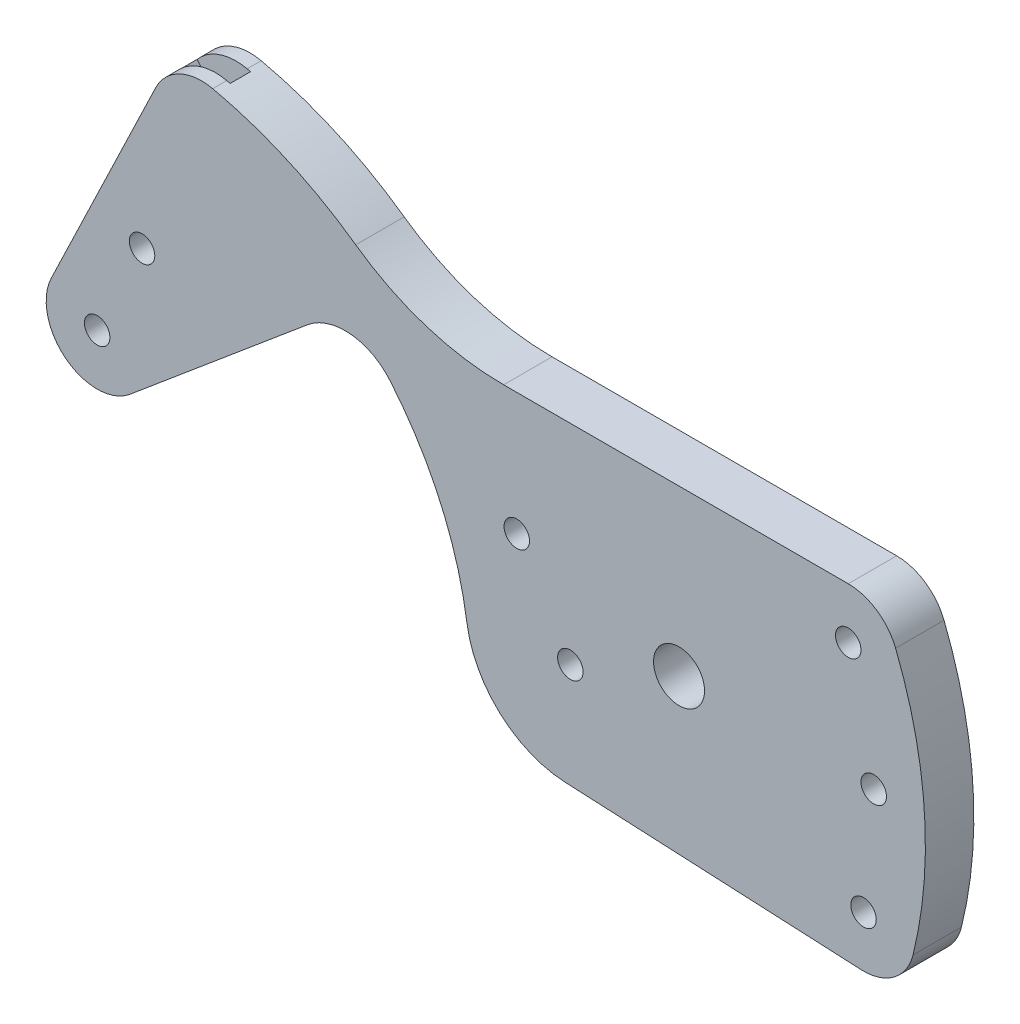
SolidWorks part; units mm, degrees
ref_plane "Front Plane" through (0, 0, 0) normal (0, 0, 1) x (1, 0, 0)
ref_plane "Top Plane" through (0, 0, 0) normal (0, 1, 0) x (1, 0, 0)
ref_plane "Right Plane" through (0, 0, 0) normal (1, 0, 0) x (0, 0, -1)
sketch "Sketch1" plane through (0, 0, 0) normal (0, 0, 1) x (1, 0, 0)
  line L1 (-5, -5) -> (5, -5) construction
  line L2 (-5, -5) -> (-5, 5) construction
  line L3 (-5, 5) -> (5, 5) construction
  line L4 (5, -5) -> (5, 5) construction
  line L5 (-5, -5) -> (5, 5) construction
  line L6 (-5, 5) -> (5, -5) construction
  line L7 (35.6989, -31.9883) -> (-22.3088, -29.1817)
  line L9 (-114.3299, 24.3337) -> (-123.1299, 6.0337)
  line L10 (-107.6899, -5.9604) -> (-72.8648, 23.2613)
  line L11 (-114.3299, 24.3337) -> (-102.6393, 48.6449)
  line L16 (-65.4725, 14.4515) -> (-108.3178, -21.5) construction
  line L17 (50.9822, -33.5) -> (-177.2181, -33.5) construction
  line L20 (-34.3975, 32.3) -> (33.1822, 32.3)
  circle A0 centre (0, 0) radius 5
  circle A1 centre (-31.8178, 8.3) radius 2.5
  circle A2 centre (-21.3178, -8.7) radius 2.5
  circle A3 centre (33.1822, 22.3) radius 2.5
  circle A4 centre (38.1822, -0.1) radius 2.5
  circle A5 centre (36.1822, -22) radius 2.5
  circle A6 centre (36.1822, -22) radius 2.5 construction
  circle A7 centre (38.1822, -0.1) radius 2.5 construction
  circle A8 centre (33.1822, 22.3) radius 2.5 construction
  circle A9 centre (-31.8178, 8.3) radius 2.5 construction
  circle A10 centre (-21.3178, -8.7) radius 2.5 construction
  arc A12 (-41.605, -11.6848) -> (-22.3088, -29.1817) centre (-21.3178, -8.7) ccw
  arc A13 (32.976, -31.8566) -> (28.2895, 32.3) centre (-34.3029, -4.5217) ccw construction
  arc A14 (45.8883, -24.4068) -> (42.4751, 25.9934) centre (-34.3029, -4.5217) ccw
  arc A15 (35.6989, -31.9883) -> (45.8883, -24.4068) centre (36.1822, -22) ccw
  arc A16 (42.4751, 25.9934) -> (33.1822, 32.3) centre (33.1822, 22.3) ccw
  circle A17 centre (-105.3178, 20) radius 2.5
  circle A18 centre (-34.3029, -4.5217) radius 82.6199 construction
  circle A19 centre (-114.1178, 1.7) radius 2.5
  circle A21 centre (-105.3178, 20) radius 2.5 construction
  circle A22 centre (-114.1178, 1.7) radius 2.5 construction
  circle A23 centre (-105.3178, 20) radius 10 construction
  arc A24 (-123.1299, 6.0337) -> (-107.6899, -5.9604) centre (-114.1178, 1.7) ccw
  arc A27 (-91.4485, 54.071) -> (-102.6393, 48.6449) centre (-93.6271, 44.3112) ccw
  circle A31 centre (-34.3029, -4.5217) radius 72.6199 construction
  arc A32 (-41.605, -11.6848) -> (-56.6627, 21.8438) centre (-108.3178, -21.5) ccw
  arc A33 (-31.0644, -26.7412) -> (-91.4485, 54.071) centre (-108.3178, -21.5) ccw
  arc A34 (-63.4016, 41.5721) -> (-34.3975, 32.3) centre (-34.3975, 82.3) ccw
  arc A35 (-56.6627, 21.8438) -> (-72.8648, 23.2613) centre (-65.4725, 14.4515) ccw
  circle A36 centre (-65.4725, 14.4515) radius 10.5004 construction
  circle A37 centre (-108.3178, -21.5) radius 67.4309 construction
  circle A38 centre (-108.3178, -21.5) radius 77.4309 construction
  circle A39 centre (-108.3178, -21.5) radius 10.5004 construction
  circle A40 centre (-108.3178, -21.5) radius 11.5004 construction
  circle A41 centre (0, 0) radius 33 construction
  point P35 (50.3427, -4.5217)
  point P37 (37.1696, 16.7103)
  point P53 (0, 0)
  point P54 (-36.0565, -0.0269)
  point P61 (0, 0)
  point P63 (28.1353, 32.5517)
  point P71 (0, 0)
  point P74 (0, 0)
  point P75 (-40.8381, -1.4887)
  point P82 (-84.8004, 52.3295)
  point P83 (-8.6809, 36.0376)
  point P84 (0, 0)
  point P85 (-38.9538, 32.297)
  point P87 (-34.3029, 32.27)
  dimension "D1" = 10
  dimension "D3" = 10
  dimension "D5" = 50
  dimension "D7" = 40
  dimension "D4" = 10
  dimension "D2" = 10
  dimension "D8" = 1
extrude "Boss-Extrude1" add sketch "Sketch1" along normal mid plane 9.5 contours A0 L4 L3 | A0 L1 L4 | A0 L2 L1 | A0 L3 L2 | A35 A32 A12 A33 A27 L11 L9 A24 L10 A17 A19 region at (6.7597, -29.2489, 0) region at (-82.3925, 21.3461, 0)
sketch "Sketch2" plane through (0, 0, 0) normal (0, 0, 1) x (1, 0, 0)
  line L0 (-93.6271, 44.3112) -> (-96.4853, 53.8941) construction
  line L2 (-93.6271, 44.3112) -> (-55.2256, -84.4436) construction
  line L3 (-91.5658, 44.926) -> (-26.3999, -37.8579)
  line L4 (-92.7566, 54.2733) -> (-93.6271, 44.3112) construction
  line L5 (-93.6271, 44.3112) -> (-104.5883, -81.1176) construction
  line L6 (-99.8125, 52.1688) -> (-93.6271, 44.3112) construction
  line L7 (-93.6271, 44.3112) -> (-27.9715, -39.095) construction
  line L8 (-101.384, 50.9317) -> (-95.6885, 43.6964)
  line L9 (-90.7642, 54.0991) -> (-91.5658, 44.926)
  line L10 (-99.8125, 52.1688) -> (-101.384, 50.9317)
  line L11 (-92.7566, 54.2733) -> (-90.7642, 54.0991)
  line L12 (-99.4217, 0.9774) -> (-73.8566, 22.429)
  line L13 (-107.6899, -5.9604) -> (-72.8648, 23.2613) construction
  line L14 (-102.5172, 52.3714) -> (-92.0745, 39.1053) construction
  line L15 (-90.6047, 55.9243) -> (-92.0745, 39.1053) construction
  line L16 (-95.6885, 43.6964) -> (-106.5807, -80.9435)
  line L18 (-95.1798, 49.5171) -> (-26.3999, -37.8579) construction
  line L19 (-95.1798, 49.5171) -> (-106.5807, -80.9435) construction
  arc A0 (-92.7566, 54.2733) -> (-99.8125, 52.1688) centre (-93.6271, 44.3112) ccw
  arc A2 (-90.6047, 55.9243) -> (-102.5172, 52.3714) centre (-93.6271, 44.3112) ccw construction
  arc A3 (-91.4485, 54.071) -> (-102.6393, 48.6449) centre (-93.6271, 44.3112) ccw construction
  point P3 (0, 0)
  point P4 (-84.0334, 42.5815)
  point P5 (0, 0)
  point P13 (-96.4853, 53.8941)
  point P27 (0, 0)
  point P30 (-79.3927, 17.7837)
  point P31 (0, 0)
  point P33 (0, 0)
  dimension "D1" = 2
  dimension "D2" = 2
extrude "Cut-Extrude1" cut sketch "Sketch2" against normal mid plane 4 contours L11 A0 L10 L8 L12 L9 region at (-90.0803, 26.917, 0)
